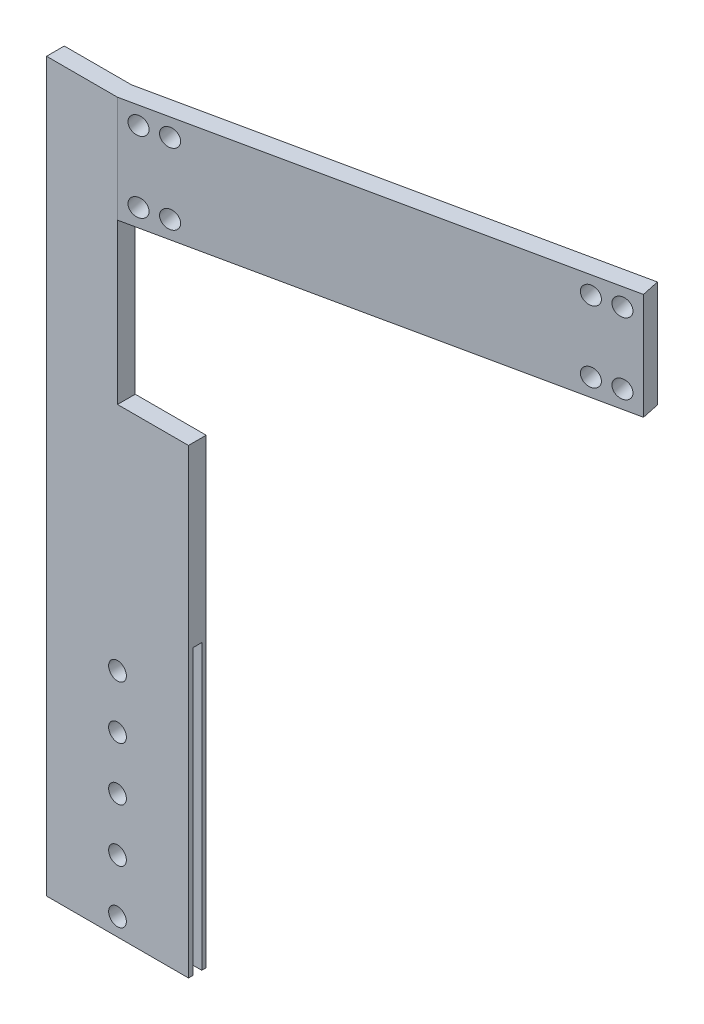
SolidWorks part; units mm, degrees
ref_plane "Front Plane" through (0, 0, 0) normal (0, 0, 1) x (1, 0, 0)
ref_plane "Top Plane" through (0, 0, 0) normal (0, 1, 0) x (1, 0, 0)
ref_plane "Right Plane" through (0, 0, 0) normal (1, 0, 0) x (0, 0, -1)
sketch "Sketch1" plane through (0, 0, 0) normal (0, 1, 0) x (1, 0, 0)
  line L0 (0, 23.6458) -> (0, -25.0113) construction
  line L1 (40, 5) -> (-40, 5)
  line L2 (-40, 5) -> (-40, 2.5)
  line L3 (-40, 2.5) -> (-30, 2.5)
  line L4 (-30, 2.5) -> (-30, -2.5)
  line L5 (-30, -2.5) -> (-40, -2.5)
  line L6 (-40, -2.5) -> (-40, -5)
  line L7 (-40, -5) -> (40, -5)
  line L8 (-30, 0) -> (30, 0) construction
  line L9 (40, -2.5) -> (40, -5)
  line L10 (30, -2.5) -> (40, -2.5)
  line L11 (30, 2.5) -> (30, -2.5)
  line L12 (40, 2.5) -> (30, 2.5)
  line L13 (40, 5) -> (40, 2.5)
  point P18 (0, -5)
  point P23 (0, 5)
  dimension "D1" = 2.5
  dimension "D2" = 10
  dimension "D3" = 10
  dimension "D4" = 80
extrude "body" add sketch "Sketch1" along normal blind 160
sketch "Sketch2" plane through (0, 0, 5) normal (0, 0, 1) x (1, 0, 0)
  line L0 (0, 0) -> (0, 160) construction
  line L1 (-40, 160) -> (40, 160) construction
  circle A0 centre (0, 10) radius 5
  dimension "D1" = 10
  dimension "D2" = 10
extrude "pin hole" cut sketch "Sketch2" against normal through all
pattern_linear "LPattern1" count 5 spacing 30 along (0, 1, 0) of "pin hole"
sketch "Sketch3" plane through (0, 0, 5) normal (0, 0, 1) x (1, 0, 0)
  line L1 (-40, 160) -> (40, 160)
  line L2 (-40, 160) -> (-40, 260)
  line L3 (-40, 260) -> (40, 260)
  line L4 (40, 160) -> (40, 260)
  line L5 (0, 260) -> (-40, 260)
  line L6 (0, 260) -> (0, 410)
  line L7 (0, 410) -> (-40, 410)
  line L8 (-40, 260) -> (-40, 410)
  point P12 (0, 260)
  line M13 (40, 160) -> (-40, 160)
  dimension "D1" = 100
  dimension "D2" = 150
  dimension "D3" = 40
extrude "spine" add sketch "Sketch3" against normal up to surface (10 mm away) contours L4 L3 L2 M13 | L3 L8 L7 L6 region at (0, 210, 5) region at (-20, 335, 5) up to face at (5, 40, -5)
sketch "Sketch8" plane through (0, 410, 0) normal (0, 1, 0) x (1, 0, 0)
  line L0 (0, -5) -> (244.5369, 46.9779)
  line L1 (244.5369, 46.9779) -> (242.4113, 56.9779)
  line L2 (242.4113, 56.9779) -> (-2.1256, 5)
  line L3 (-40, 5) -> (0, 5) construction
  line L4 (-2.1256, 5) -> (0, -5)
  line L5 (0, -5) -> (40, -5) construction
  line L6 (0, -5) -> (-40, -5) construction
  dimension "D1" = 12
  dimension "D2" = 250
extrude "slider holder" add sketch "Sketch8" against normal blind 60
sketch "Sketch9" plane through (1.0168, 0, 4.7839) normal (0.2079, 0, 0.9781) x (0.9781, 0, -0.2079)
  line L0 (-1.0396, 380) -> (248.9604, 380) construction
  line L1 (-1.0396, 350) -> (-1.0396, 410) construction
  line L2 (248.9604, 350) -> (248.9604, 410) construction
  line L3 (123.9604, 350) -> (123.9604, 410) construction
  line L4 (-1.0396, 350) -> (248.9604, 350) construction
  line L5 (-1.0396, 410) -> (248.9604, 410) construction
  circle A0 centre (8.9604, 400) radius 5
  circle A1 centre (23.9604, 400) radius 5
  circle A2 centre (8.9604, 360) radius 5
  circle A3 centre (23.9604, 360) radius 5
  circle A4 centre (223.9604, 360) radius 5
  circle A5 centre (238.9604, 360) radius 5
  circle A6 centre (238.9604, 400) radius 5
  circle A7 centre (223.9604, 400) radius 5
  dimension "D1" = 10
  dimension "D2" = 20
  dimension "D3" = 15
  dimension "D4" = 10
extrude "slider fixture holes" cut sketch "Sketch9" against normal through all
